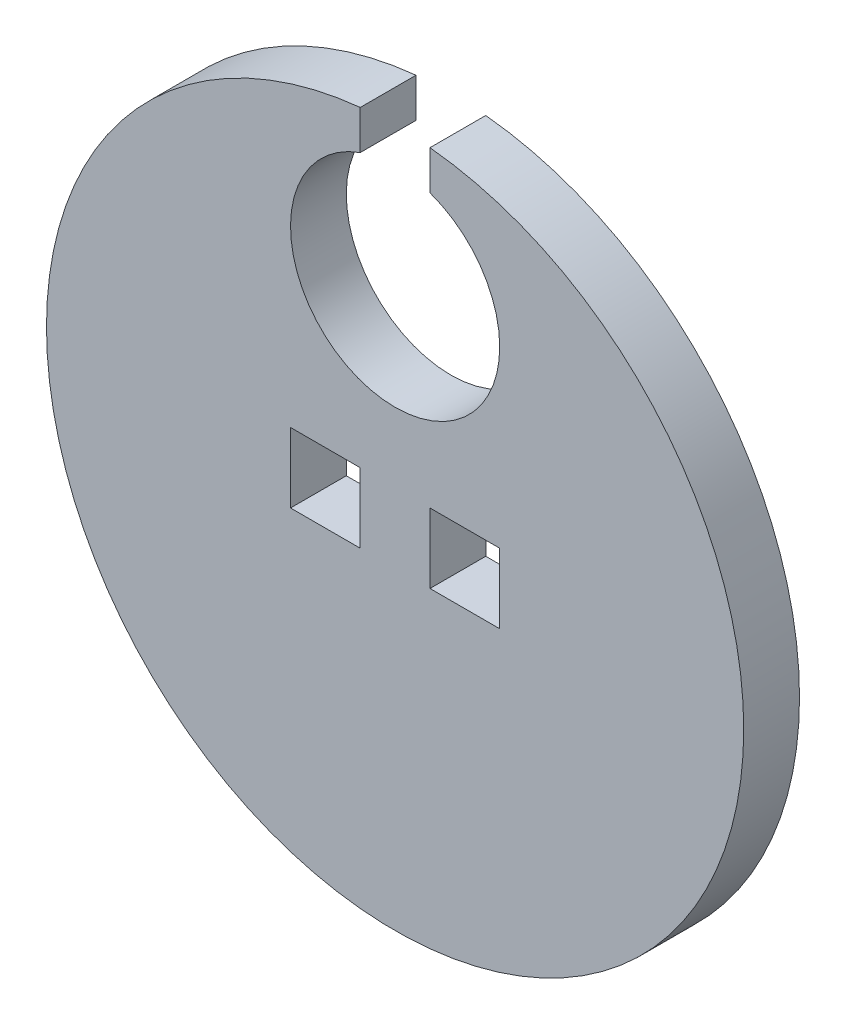
SolidWorks part; units mm, degrees
ref_plane "Front Plane" through (0, 0, 0) normal (0, 0, 1) x (1, 0, 0)
ref_plane "Top Plane" through (0, 0, 0) normal (0, 1, 0) x (1, 0, 0)
ref_plane "Right Plane" through (0, 0, 0) normal (1, 0, 0) x (0, 0, -1)
sketch "Sketch1" plane through (0, 0, 0) normal (0, 0, 1) x (1, 0, 0)
  line L1 (1.5875, -1.5875) -> (4.7625, -1.5875)
  line L2 (1.5875, -1.5875) -> (1.5875, 1.5875)
  line L3 (1.5875, 1.5875) -> (4.7625, 1.5875)
  line L4 (4.7625, -1.5875) -> (4.7625, 1.5875)
  line L5 (1.5875, -1.5875) -> (4.7625, 1.5875) construction
  line L6 (1.5875, 1.5875) -> (4.7625, -1.5875) construction
  line L7 (-4.7625, -1.5875) -> (-1.5875, -1.5875)
  line L8 (-4.7625, -1.5875) -> (-4.7625, 1.5875)
  line L9 (-4.7625, 1.5875) -> (-1.5875, 1.5875)
  line L10 (-1.5875, -1.5875) -> (-1.5875, 1.5875)
  line L11 (-4.7625, -1.5875) -> (-1.5875, 1.5875) construction
  line L12 (-4.7625, 1.5875) -> (-1.5875, -1.5875) construction
  circle A0 centre (0, 0) radius 15.875
  point P3 (3.175, 0)
  point P8 (-3.175, 0)
  dimension "D1" = 31.75
  dimension "D2" = 3.175
  dimension "D3" = 3.175
  dimension "D4" = 1.5875
extrude "Boss-Extrude1" add sketch "Sketch1" along normal blind 2.54 contours L1 L4 L3 L2 | L7 L10 L9 L8 | A0 region at (3.175, 0, 0) region at (-3.175, 0, 0)
sketch "Sketch2" plane through (0, 0, 2.54) normal (0, 0, 1) x (1, 0, 0)
  line L0 (-1.5875, 14.0151) -> (-1.5875, 19.05)
  line L1 (-1.5875, 19.05) -> (1.5875, 19.05)
  line L2 (1.5875, 19.05) -> (1.5875, 14.0151)
  arc A0 (-1.5875, 14.0151) -> (1.5875, 14.0151) centre (0, 9.525) ccw
  circle A1 centre (0, 9.525) radius 1.5875 construction
  dimension "D1" = 9.525
  dimension "D3" = 3.175
  dimension "D2" = 9.525
  dimension "D4" = 9.525
extrude "Cut-Extrude1" cut sketch "Sketch2" against normal blind 2.54
